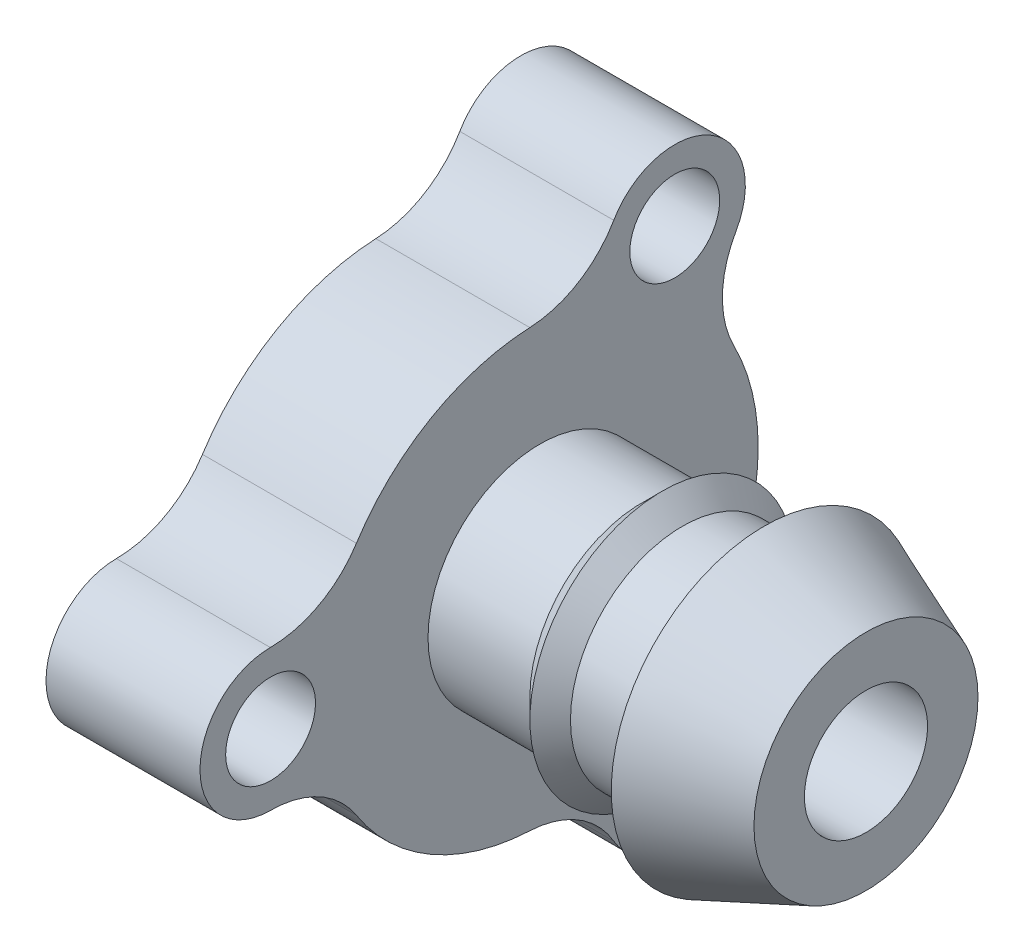
SolidWorks part; units mm, degrees
ref_plane "Front Plane" through (0, 0, 0) normal (0, 0, 1) x (1, 0, 0)
ref_plane "Top Plane" through (0, 0, 0) normal (0, 1, 0) x (1, 0, 0)
ref_plane "Right Plane" through (0, 0, 0) normal (1, 0, 0) x (0, 0, -1)
sketch "Sketch1" plane through (0, 0, 0) normal (0, 1, 0) x (1, 0, 0)
  line L0 (0, 0) -> (-12.7, 0)
  line L1 (0, 0) -> (0, 4.365)
  line L2 (0, 4.365) -> (-3.97, 5.955)
  line L3 (-3.97, 5.955) -> (-3.97, 4.365)
  line L4 (0, 4.365) -> (-19.3321, 4.365) construction
  line L5 (-3.97, 4.365) -> (-7.15, 4.365)
  line L6 (-7.15, 4.365) -> (-7.94, 5.155)
  line L7 (-7.94, 5.155) -> (-8.73, 4.365)
  line L8 (-8.73, 4.365) -> (-12.7, 4.365)
  line L9 (-12.7, 4.365) -> (-12.7, 0)
  dimension "D1" = 12.7
  dimension "D2" = 4.365
  dimension "D3" = 1.59
  dimension "D4" = 3.97
  dimension "D5" = 7.94
  dimension "D6" = 0.79
revolve "Revolve1" add sketch "Sketch1" angle 360 about L0
sketch "Sketch4" plane through (-12.7, 0, 0) normal (-1, 0, 0) x (0, 0, 1)
  circle A0 centre (0, 0) radius 2.4
  circle A1 centre (0, 0) radius 8.5
  circle A2 centre (0, 0) radius 3.8
  point P6 (-0.7964, -0.4799)
  circle M2 centre (0, 0) radius 4.365
  dimension "D1" = 4.8
  dimension "D2" = 17
  dimension "D3" = 7.6
extrude "Boss-Extrude1" add sketch "Sketch4" along normal blind 2 contours A1 M2 | A2 A0 | A2 M2 region at (-12.7, 0, -8.2596) region at (-12.7, 0, -3.6925) region at (-12.7, 0, -4.2415)
extrude "Boss-Extrude2" add sketch "Sketch4<3>" along normal blind 4 from surface contours A1 M2 region at (-12.7, 0, -8.2596) starting at face at (-14.7, 0, 8.5)
sketch "Sketch4<3>" plane through (-12.7, 0, 0) normal (-1, 0, 0) x (0, 0, 1) same geometry as "Sketch4"
extrude "Cut-Extrude2" cut sketch "Sketch4<4>" against normal through all contours A0 region at (-12.7, 0, 0)
sketch "Sketch4<4>" plane through (-12.7, 0, 0) normal (-1, 0, 0) x (0, 0, 1) same geometry as "Sketch4"
sketch "Sketch5" plane through (-18.7, 0, 0) normal (-1, 0, 0) x (0, 0, 1)
  line L0 (0, 0) -> (8.5, 0) construction
  circle A0 centre (0, 0) radius 6.0824
  circle A1 centre (0, 0) radius 8.5 construction
  dimension "D1" = 12.1647
sweep "Cut-Sweep1" cut path "Sketch5" circular profile diameter 1.778 parameters "D3"=1.778
sketch "Sketch14" plane through (-18.7, 0, 0) normal (-1, 0, 0) x (0, 0, 1)
  circle A0 centre (0, 0) radius 8.5
  circle A1 centre (0, 0) radius 8.5 construction
  circle A2 centre (0, 0) radius 10.5 construction
  circle A3 centre (10.5, 0) radius 2.75
  circle A4 centre (10.5, 0) radius 1.75
  circle A5 centre (-5.25, -9.0933) radius 1.75
  circle A6 centre (-5.25, -9.0933) radius 2.75
  circle A7 centre (-5.25, 9.0933) radius 1.75
  circle A8 centre (-5.25, 9.0933) radius 2.75
  point P10 (-5.9136, 7.832)
  point P11 (0, 0)
  point P17 (0, 0)
  circle M6 centre (0, 0) radius 8.5
  dimension "D1" = 21
  dimension "D2" = 5.5
  dimension "D3" = 3.5
  dimension "D4" = 3
extrude "Boss-Extrude3" add sketch "Sketch14" against normal up to surface (6 mm away) contours A0 A8 A7 | A0 A8 | A0 A6 A5 | A0 A6 | A4 A0 A3 M6 | A0 A3 M6 region at (-18.7, 0, 8.1633) region at (-18.7, 0.8565, 8.5309) region at (-18.7, 7.0696, -4.0816) region at (-18.7, 7.4284, -4.2888) region at (-18.7, -8.5813, -2.6271) region at (-18.7, -7.0696, -4.0816)
fillet "Fillet3" radius 4 6 edges at (-15.7, -1.6897, 8.3304) (-15.7, -6.3694, -5.6285) (-15.7, -8.0592, -2.7018) (-15.7, 8.0592, -2.7018) (-15.7, 6.3694, -5.6285) (-15.7, 1.6897, 8.3304)
chamfer "Chamfer1" distance 1 angle 45 1 edges at (-14.7, 0, 2.4)
equation "\"WallThick\"= 1.2'thickness of wall for printer"
equation "\"dHole\"= 3.3'diameter of screw hole"
